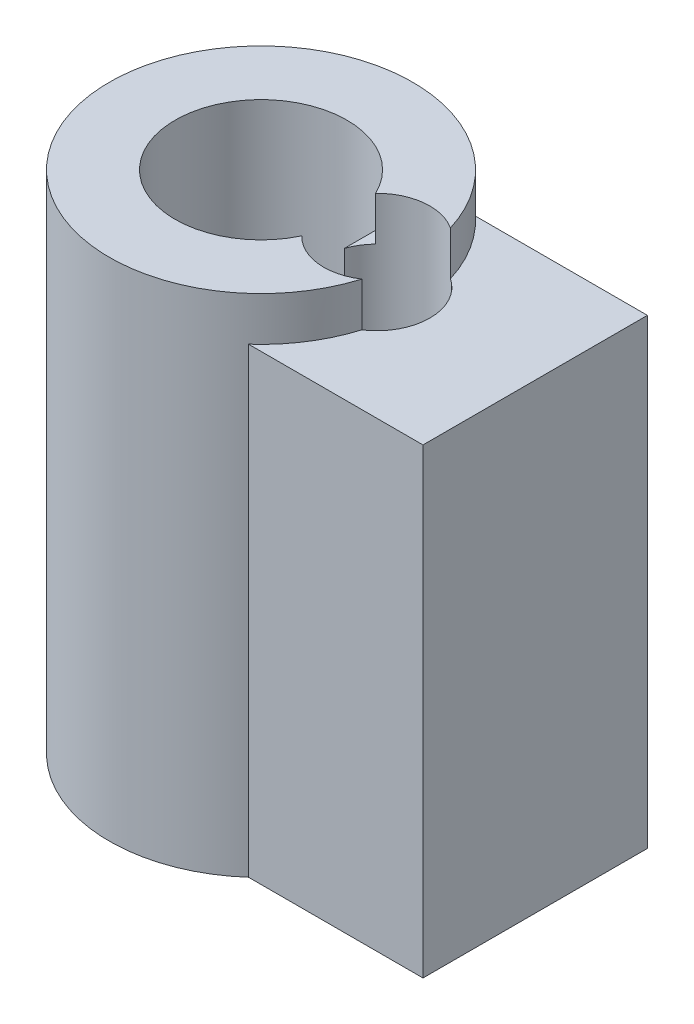
SolidWorks part; units mm, degrees
ref_plane "Front Plane" through (0, 0, 0) normal (0, 0, 1) x (1, 0, 0)
ref_plane "Top Plane" through (0, 0, 0) normal (0, 1, 0) x (1, 0, 0)
ref_plane "Right Plane" through (0, 0, 0) normal (1, 0, 0) x (0, 0, -1)
sketch "Sketch1" plane through (0, 0, 0) normal (0, 1, 0) x (1, 0, 0)
  circle A0 centre (0, 0) radius 6
extrude "Boss-Extrude1" add sketch "Sketch1" along normal blind 20
sketch "Sketch2" plane through (0, 20, 0) normal (0, 1, 0) x (1, 0, 0)
  circle A0 centre (0, 0) radius 3.4
extrude "Cut-Extrude1" cut sketch "Sketch2" against normal blind 13.55 contours A0
ref_plane "Plane1" through (0, 18.26, 0) normal (0, 1, 0) x (1, 0, 0)
ref_axis "Axis1" through (0, 6.45, 0) along (0, 1, 0)
ref_point "Point2"
sketch "Sketch5" plane through (0, 18.26, 0) normal (0, 1, 0) x (1, 0, 0)
  line L0 (0, 0) -> (2.6, 0) construction
  line L2 (2.6, -4.4818) -> (10.8879, -4.4818)
  line L3 (2.6, -4.4818) -> (2.6, 4.3942)
  line L4 (2.6, 4.3942) -> (10.8879, 4.3942)
  line L5 (10.8879, -4.4818) -> (10.8879, 4.3942)
  point P7 (0, 0)
extrude "Boss-Extrude2" add sketch "Sketch5" against normal up to surface (18.26 mm away) up to face at (0, 0, 6)
sketch "Sketch8" plane through (0, 18.26, 0) normal (0, 1, 0) x (1, 0, 0)
  line L0 (2.6, 0) -> (5.1536, 0) construction
  circle A0 centre (4.5805, 0) radius 2.1
  point P6 (3.9812, 0)
  point P7 (4.7106, 0)
  point P8 (4.5805, 0)
extrude "Cut-Extrude6" cut sketch "Sketch8" against normal blind 30 and the other way blind 30 contours A0
